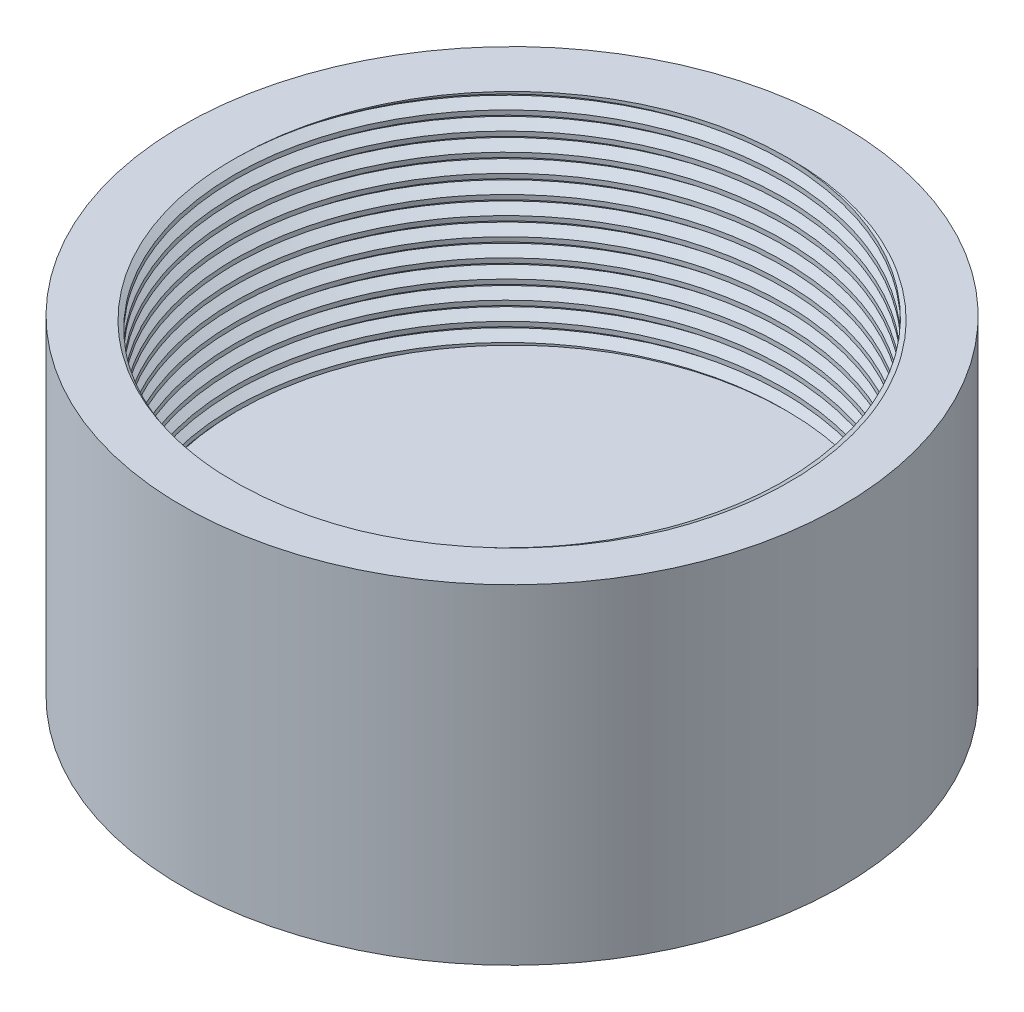
SolidWorks part; units mm, degrees
ref_plane "Front Plane" through (0, 0, 0) normal (0, 0, 1) x (1, 0, 0)
ref_plane "Top Plane" through (0, 0, 0) normal (0, 1, 0) x (1, 0, 0)
ref_plane "Right Plane" through (0, 0, 0) normal (1, 0, 0) x (0, 0, -1)
sketch "Sketch1" plane through (0, 0, 0) normal (0, 1, 0) x (1, 0, 0)
  circle A0 centre (0, 0) radius 38.1
  dimension "D1" = 76.2
extrude "Boss-Extrude1" add sketch "Sketch1" along normal blind 38.1 contours A0
sketch "Sketch2" plane through (0, 38.1, 0) normal (0, 1, 0) x (1, 0, 0)
  circle A0 centre (0, 0) radius 31.75
  dimension "D1" = 63.5
extrude "Cut-Extrude1" cut sketch "Sketch2" against normal blind 25.4
thread "Thread1" pitch 2.1167 method cut profile "Thread Profile1" start angle 0, offset 6.35, length 35.4, pitch 2.1167, diameter 63.5
ref_plane "Plane1" through (-31.75, 44.45, 0) normal (0, 0, 1) x (-1, 0, 0)
sketch "Thread Profile1" plane through (-31.75, 44.45, 0) normal (0, 0, 1) x (-1, 0, 0)
  line L0 (0, 0) -> (0, 2.1167) construction
  line L1 (0, 0) -> (1.1457, 0.6615)
  line L2 (1.1457, 0.6615) -> (1.1457, 0.926)
  line L3 (1.1457, 0.926) -> (0, 1.5875)
  line L4 (1.1457, 0.7937) -> (0, 0.7937) construction
  line L11 (0, 0) -> (0, 1.5875)
  point P2 (0, 0)
  dimension "Pitch" = 2.1167
  dimension "Profile_Angle" = 60
  dimension "Profile_Land" = 0.2646
  dimension "Profile_Height" = 1.1457
